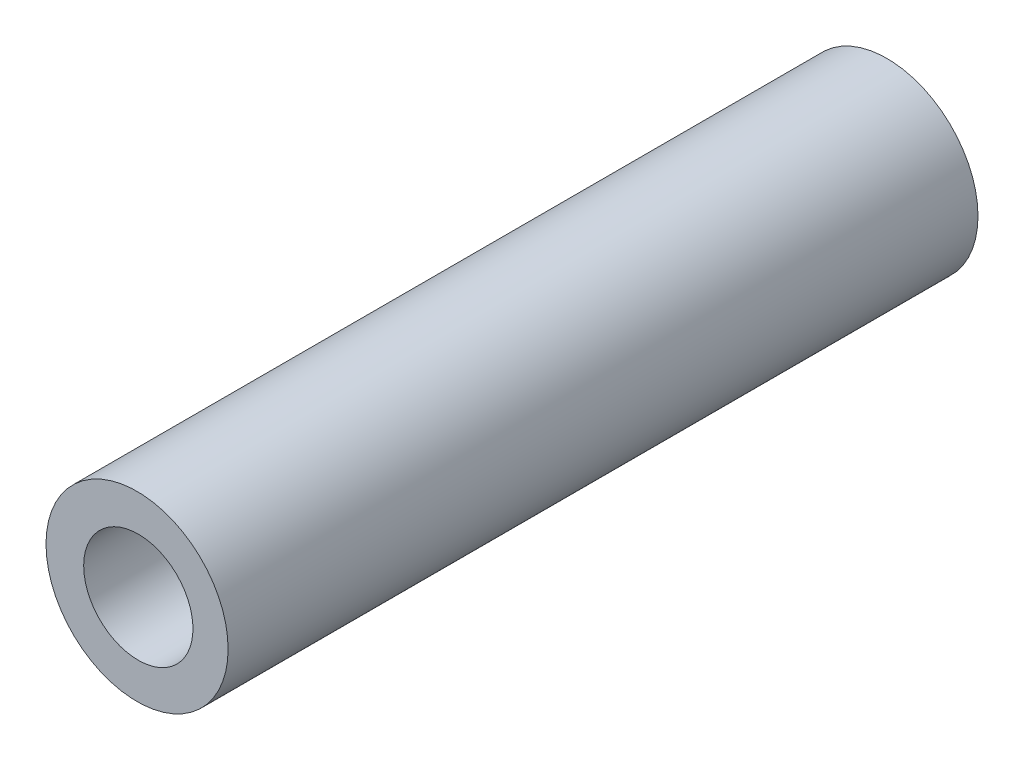
SolidWorks part; units mm, degrees
material "Plastique personnalisé"
ref_plane "Plan de face" through (0, 0, 0) normal (0, 0, 1) x (1, 0, 0)
ref_plane "Plan de dessus" through (0, 0, 0) normal (0, 1, 0) x (1, 0, 0)
ref_plane "Plan de droite" through (0, 0, 0) normal (1, 0, 0) x (0, 0, -1)
sketch "Esquisse1" plane through (0, 0, 0) normal (0, 0, 1) x (1, 0, 0)
  circle A0 centre (0, 0) radius 1.5
  circle A1 centre (-0.0343, 0) radius 2.5
extrude "Boss.-Extru.1" add sketch "Esquisse1" along normal blind 20.59
